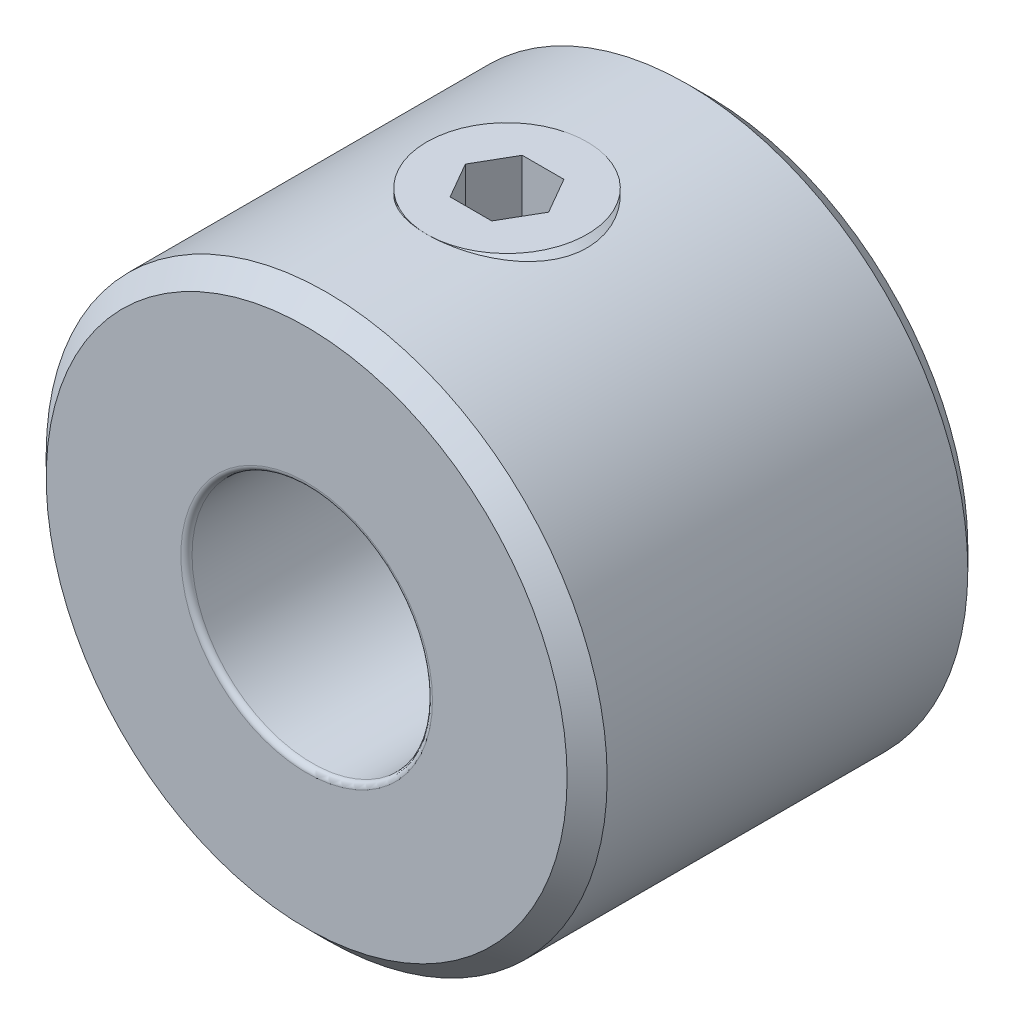
SolidWorks part; units mm, degrees
ref_plane "Front Plane" through (0, 0, 0) normal (0, 0, 1) x (1, 0, 0)
ref_plane "Top Plane" through (0, 0, 0) normal (0, 1, 0) x (1, 0, 0)
ref_plane "Right Plane" through (0, 0, 0) normal (1, 0, 0) x (0, 0, -1)
sketch "Sketch1" plane through (0, 0, 0) normal (0, 0, 1) x (1, 0, 0)
  line L0 (0, 3.5) -> (0, 0) construction
  line L1 (0, 0) -> (-2.4749, -2.4749) construction
  circle A0 centre (0, 0) radius 3.5
  circle A1 centre (0, 0) radius 1.5
  point P4 (3.5, 0)
  point P5 (0, 3.5)
  dimension "Bore Dia" = 3
  dimension "OD" = 7
  dimension "D1" = 135
extrude "Extrude1" add sketch "Sketch1" along normal blind 5
ref_plane "Plane1" through (0, 3.5, 0) normal (0, 1, 0) x (-1, 0, 0)
sketch "Sketch2" plane through (0, 3.5, 0) normal (0, 1, 0) x (-1, 0, 0)
  line L0 (0, 0) -> (0, 5) construction
  line L2 (3.5, 5) -> (-3.5, 5) construction
  circle A0 centre (0, 2.5) radius 1
  point P8 (0, 2.5)
  dimension "Set Screw Dia" = 2
extrude "Cut-Extrude1" cut sketch "Sketch2" against normal up to surface (3.5 mm away) up to plane "Top Plane"
ref_plane "Plane2" through (0, 0, 2.5) normal (0, 0, 1) x (1, 0, 0)
sketch "Sketch3" plane through (0, 0, 2.5) normal (0, 0, 1) x (1, 0, 0)
  line L0 (-0.9, 3.5) -> (-1, 3.43)
  line L1 (0, 0.8293) -> (0, 3.5)
  line L3 (-1, 0.952) -> (-1, 3.43)
  line L4 (0, 3.5) -> (-0.9, 3.5)
  line L5 (0, 0.5) -> (0, 0) construction
  line L6 (-1, 3.43) -> (0, 3.43) construction
  line L7 (0, 0.8293) -> (-0.548, 0.5)
  line L8 (-0.548, 0.5) -> (-1, 0.952)
  point P1 (-0.548, 0.5)
  dimension "Screw Length" = 3
  dimension "D3" = 2
  dimension "D1" = 1.8
  dimension "D7" = 1
  dimension "D2" = 35
  dimension "D4" = 59
  dimension "D5" = 45
revolve "Revolve1" add sketch "Sketch3" angle 360 about L1
sketch "Sketch4" plane through (0, 3.5, 0) normal (0, 1, 0) x (0, 0, -1)
  line L0 (-2.5, 0.5196) -> (-2.5, -0.5196) construction
  line L1 (-2.5, 0.5196) -> (-2.95, 0.2598)
  line L2 (-2.95, 0.2598) -> (-2.95, -0.2598)
  line L3 (-2.95, -0.2598) -> (-2.5, -0.5196)
  line L4 (-2.5, -0.5196) -> (-2.05, -0.2598)
  line L5 (-2.05, -0.2598) -> (-2.05, 0.2598)
  line L6 (-2.05, 0.2598) -> (-2.5, 0.5196)
  circle A0 centre (-2.5, 0) radius 0.45 construction
  circle A1 centre (-2.5, 0) radius 0.5196 construction
  dimension "D1" = 1.0392
  dimension "Hex" = 0.9
extrude "Cut-Extrude2" cut sketch "Sketch4" against normal blind 0.72
fillet "Fillet1" radius 0.07 2 edges at (1.5, 0, 0) (1.5, 0, 5)
chamfer "Chamfer1" distance 0.25 angle 45 2 edges at (3.5, 0, 5) (3.5, 0, 0)
sketch "Sketch5" plane through (0, 3.5, 0) normal (0, 1, 0) x (1, 0, 0)
  circle A0 centre (0, -2.5) radius 1 construction
  circle A1 centre (0, -2.5) radius 1
curve "Helix/Spiral1" pitch 0.4 height 3 radius 1 centre (0, 3.5, 2.5) axis (0, -1, 0) start towards (-1, 0, 0) parameters "Pitch"=0.4
ref_plane "Plane3" through (0, 0, 2.5) normal (0, 0, 1) x (1, 0, 0)
sketch "Sketch9" plane through (0, 0, 2.5) normal (0, 0, 1) x (1, 0, 0)
  line L0 (-1, 3.5) -> (-1, 3.85)
  line L1 (-1, 3.85) -> (-0.7402, 3.7)
  line L2 (-0.7402, 3.7) -> (-0.7402, 3.65)
  line L3 (-0.7402, 3.65) -> (-1, 3.5)
  line L4 (-1, 3.675) -> (-0.7402, 3.675) construction
  line L5 (-0.8701, 3.575) -> (-0.8701, 3.775) construction
  dimension "D1" = 0.05
  dimension "D2" = 0.2
  dimension "D3" = 60
sweep "Cut-Sweep2" cut profiles "Sketch9" path "Helix/Spiral1" align with end faces yes
sketch "Sketch10" plane through (0, 3.5, 0) normal (0, 1, 0) x (1, 0, 0)
  line L0 (-0.2598, -2.05) -> (-0.5196, -2.5) construction
  line L1 (-0.5196, -2.5) -> (-0.2598, -2.95) construction
  line L2 (-0.2598, -2.95) -> (0.2598, -2.95) construction
  line L3 (0.2598, -2.95) -> (0.5196, -2.5) construction
  line L4 (0.5196, -2.5) -> (0.2598, -2.05) construction
  line L5 (0.2598, -2.05) -> (-0.2598, -2.05) construction
  line L6 (-0.2598, -2.05) -> (-0.5196, -2.5)
  line L7 (-0.5196, -2.5) -> (-0.2598, -2.95)
  line L8 (-0.2598, -2.95) -> (0.2598, -2.95)
  line L9 (0.2598, -2.95) -> (0.5196, -2.5)
  line L10 (0.5196, -2.5) -> (0.2598, -2.05)
  line L11 (0.2598, -2.05) -> (-0.2598, -2.05)
  circle A0 centre (0, -2.5) radius 1 construction
  circle A1 centre (0, -2.5) radius 1
extrude "Boss-Extrude1" add sketch "Sketch10" against normal through all draft 60
ref_plane "Contact Plane 1" through (0, 0, 5) normal (0, 0, 1) x (1, 0, 0)
ref_plane "Contact Plane 2" through (0, 0, 0) normal (0, 0, -1) x (-1, 0, 0)
ref_plane "Contact Plane 3" through (0, 0.5, 0) normal (0, -1, 0) x (-1, 0, 0)
ref_axis "Central Axis 1" through (0, 0, 4.93) along (0, 0, -1)
equation "\"D1@Fillet1\" = \"OD@Sketch1\"*.01"
equation "\"D1@Cut-Extrude2\" = \"Hex@Sketch4\"*.8"
equation "\"D3@Sketch3\"=\"Set Screw Dia@Sketch2\""
equation "\"D1@Sketch3\"=\"Set Screw Dia@Sketch2\"*.9"
equation "\"D3@Helix/Spiral1\"=\"Screw Length@Sketch3\""
equation "\"D1@Sketch9\"=\"Pitch@Helix/Spiral1\"*.125"
equation "\"D2@Sketch9\"=\"Pitch@Helix/Spiral1\"*.50"
